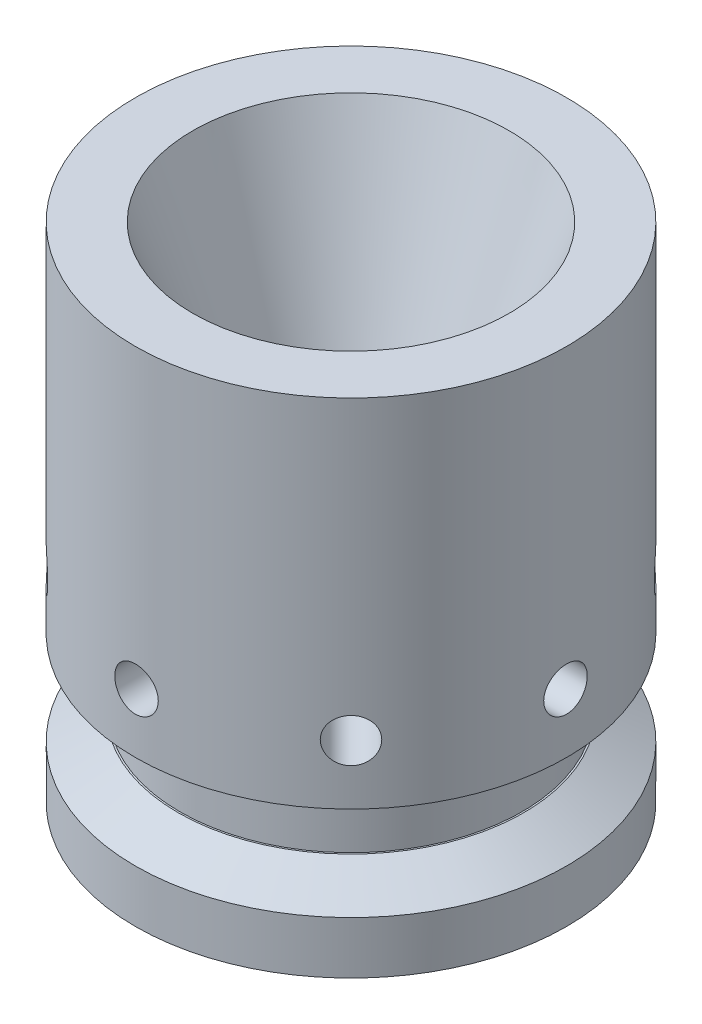
SolidWorks part; units mm, degrees
ref_plane "Front" through (0, 0, 0) normal (0, 0, 1) x (1, 0, 0)
ref_plane "Top" through (0, 0, 0) normal (0, 1, 0) x (1, 0, 0)
ref_plane "Right" through (0, 0, 0) normal (1, 0, 0) x (0, 0, -1)
sketch "Sketch2" plane through (0, 0, 0) normal (0, 0, 1) x (1, 0, 0)
  line L0 (0, 19.1415) -> (0, -24.752) construction
  line L1 (-15.8413, 0) -> (18.4815, 0) construction
  line L2 (-15.8413, 2) -> (18.4815, 2) construction
  line L3 (-2.5, 0) -> (-2.5, 2)
  line L4 (-10.9, 21.0703) -> (-10.9, -1) construction
  line L5 (-2.5, 0) -> (-10.9, -8.4)
  line L6 (-10.9, -8.4) -> (-10.9, -4.5)
  line L7 (-18.3668, 17) -> (19.9717, 17) construction
  line L8 (-2.5, 2) -> (-8, 17)
  line L9 (-8, 17) -> (-10.9, 17)
  line L10 (-10.9, 17) -> (-10.9, 2)
  line L11 (-10.9, -1) -> (-10.9, 2)
  line L12 (-10.9, -1) -> (-8.65, -1)
  line L14 (-10.9, -4.5) -> (-8.65, -4.5)
  line L15 (-8.65, -1) -> (-8.65, -4.5)
  line L16 (-10.9, -4.5) -> (-10.9, -24.752) construction
  dimension "D1" = 10.9
  dimension "D2" = 2
  dimension "D3" = 45
  dimension "D4" = 15
  dimension "D5" = 3.5
  dimension "ThrottleRadius" = 2.5
  dimension "NozzleRadius" = 8
  dimension "D6" = 2.25
  dimension "D7" = 1
revolve "Revolve1" add sketch "Sketch2" angle 360 about L0
ref_plane "Plane1" through (-10.9, 0, 0) normal (-1, 0, 0) x (0, 0, 1)
sketch "Sketch3" plane through (-10.9, 0, 0) normal (-1, 0, 0) x (0, 0, 1)
  line L0 (0, 17) -> (0, -8.4987) construction
  line L1 (8, 17) -> (-8, 17) construction
  line L2 (10.9, 17) -> (-10.9, 17) construction
  circle A0 centre (0, 2) radius 1.1
  dimension "D1" = 2.2
  dimension "D2" = 15
extrude "Cut-Extrude1" cut sketch "Sketch3" against normal blind 6
ref_axis "Axis1" through (0, 0, 0) along (0, 1, 0)
pattern_circular "CirPattern1" count 8 over 360 about axis through (0, 0, 0) along (0, 1, 0) of "Cut-Extrude1"
chamfer "Chamfer2" distance 1.25 angle 60 1 edges at (0, -4.5, 10.9) first distance on face at (0, -8.4, 10.9)
